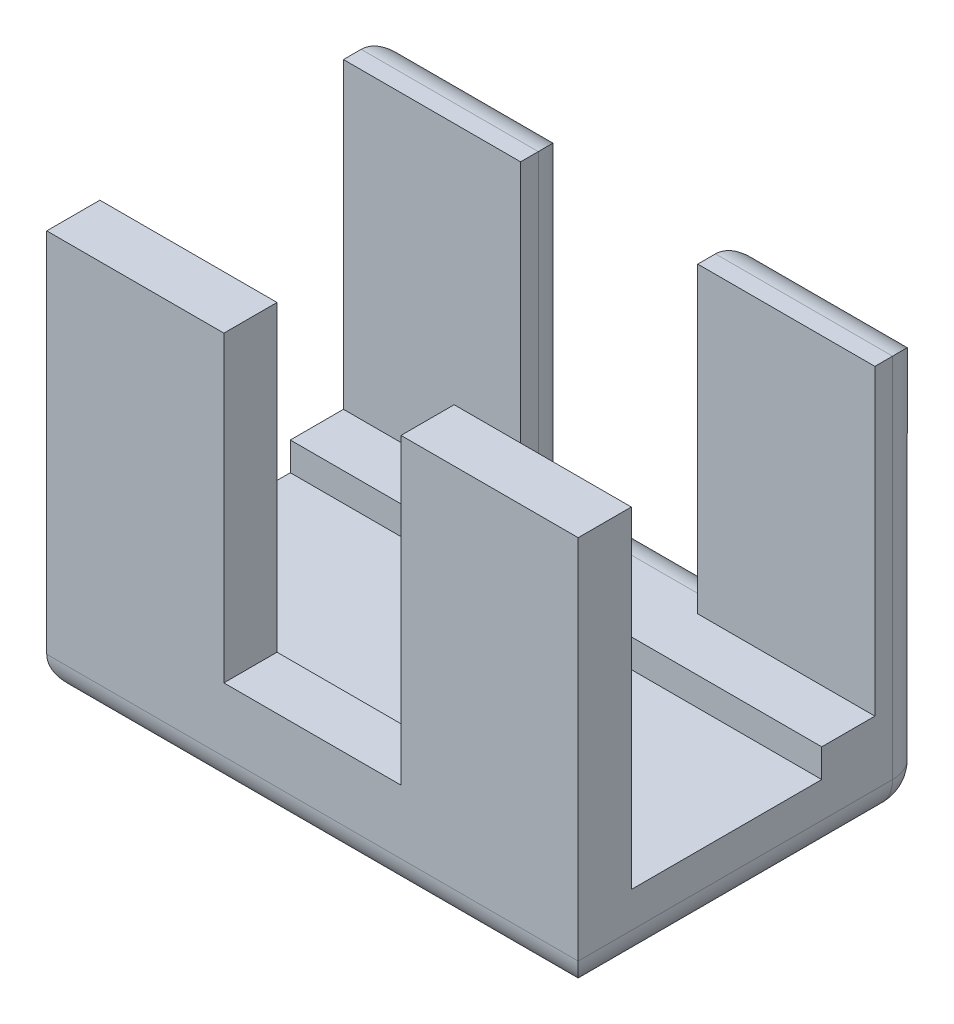
SolidWorks part; units mm, degrees
ref_plane "Front Plane" through (0, 0, 0) normal (0, 0, 1) x (1, 0, 0)
ref_plane "Top Plane" through (0, 0, 0) normal (0, 1, 0) x (1, 0, 0)
ref_plane "Right Plane" through (0, 0, 0) normal (1, 0, 0) x (0, 0, -1)
sketch "Sketch1" plane through (0, 0, 0) normal (0, 1, 0) x (1, 0, 0)
  line L1 (0, 0) -> (30, 0)
  line L2 (0, 0) -> (0, 19.75)
  line L3 (0, 19.75) -> (30, 19.75)
  line L4 (30, 0) -> (30, 19.75)
  dimension "D1" = 30
  dimension "D2" = 19.75
extrude "Boss-Extrude1" add sketch "Sketch1" along normal blind 4
sketch "Sketch2" plane through (0, 4, 0) normal (0, 1, 0) x (1, 0, 0)
  line L0 (30, 0) -> (30, 19.75) construction
  line L1 (0, 19.75) -> (30, 19.75)
  line L2 (0, 19.75) -> (0, 13.75)
  line L3 (0, 13.75) -> (30, 13.75)
  line L4 (30, 19.75) -> (30, 13.75)
  dimension "D1" = 6
extrude "Boss-Extrude2" add sketch "Sketch2" along normal blind 1.601
sketch "Sketch3" plane through (0, 4, 0) normal (0, 1, 0) x (1, 0, 0)
  line L1 (0, 0) -> (10, 0)
  line L2 (0, 0) -> (0, 3)
  line L3 (0, 3) -> (10, 3)
  line L4 (10, 0) -> (10, 3)
  line L5 (30, 0) -> (20, 0)
  line L6 (30, 0) -> (30, 3)
  line L7 (30, 3) -> (20, 3)
  line L8 (20, 0) -> (20, 3)
  dimension "D1" = 10
  dimension "D2" = 3
extrude "Boss-Extrude3" add sketch "Sketch3" along normal blind 18.7
sketch "Sketch4" plane through (0, 5.601, 0) normal (0, 1, 0) x (1, 0, 0)
  line L1 (0, 19.75) -> (10, 19.75)
  line L2 (0, 19.75) -> (0, 16.75)
  line L3 (0, 16.75) -> (10, 16.75)
  line L4 (10, 19.75) -> (10, 16.75)
  line L5 (30, 19.75) -> (20, 19.75)
  line L6 (30, 19.75) -> (30, 16.75)
  line L7 (30, 16.75) -> (20, 16.75)
  line L8 (20, 19.75) -> (20, 16.75)
  dimension "D1" = 10
  dimension "D2" = 3
extrude "Boss-Extrude4" add sketch "Sketch4" along normal blind 17.099
sketch "Sketch5" plane through (0, 4, 0) normal (0, 1, 0) x (1, 0, 0)
  line L1 (10, 3) -> (20, 3)
  line L2 (10, 3) -> (10, 0)
  line L3 (10, 0) -> (20, 0)
  line L4 (20, 3) -> (20, 0)
extrude "Boss-Extrude5" add sketch "Sketch5" along normal blind 1.601
fillet "Fillet1" radius 2 11 edges at (30, 11.35, -19.75) (25, 22.7, -19.75) (20, 14.1505, -19.75) (15, 5.601, -19.75) (10, 14.1505, -19.75) (5, 22.7, -19.75) (0, 11.35, -19.75) (15, 0, 0) (30, 0, -9.875) (15, 0, -19.75) (0, 0, -9.875)
